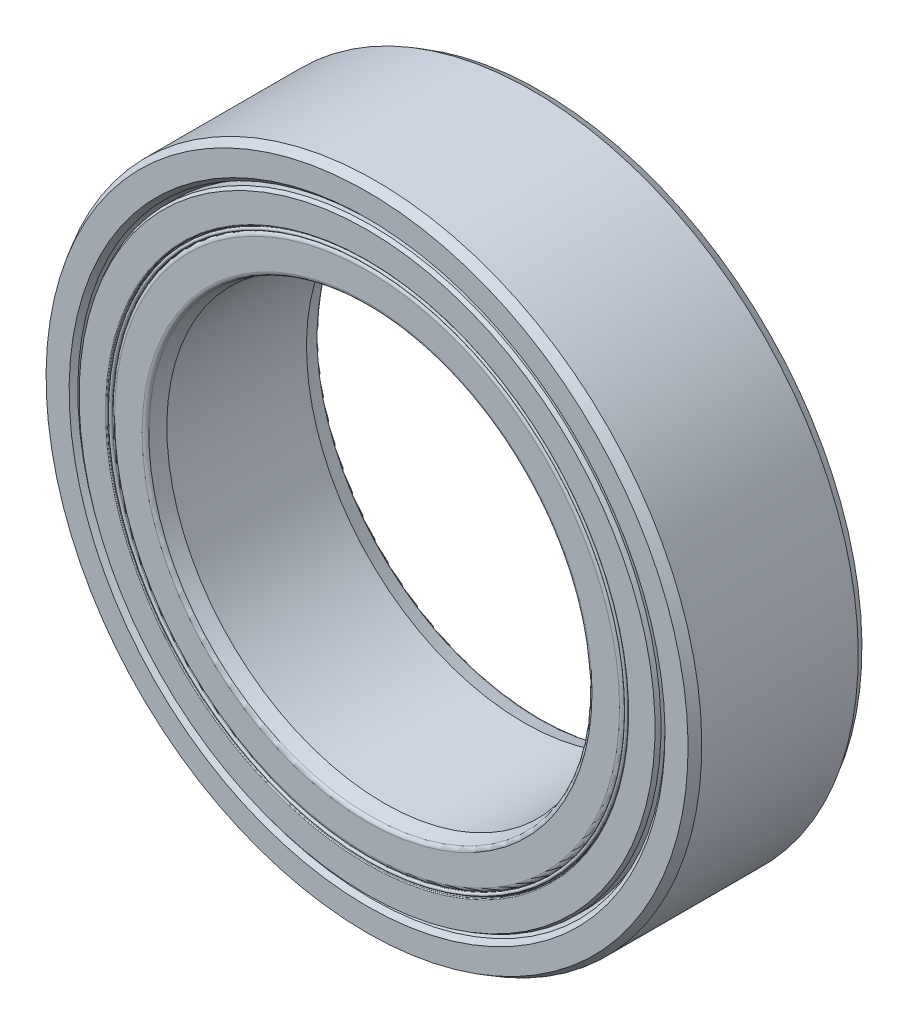
SolidWorks part; units mm, degrees
ref_plane "Front Plane" through (0, 0, 0) normal (0, 0, 1) x (1, 0, 0)
ref_plane "Top Plane" through (0, 0, 0) normal (0, 1, 0) x (1, 0, 0)
ref_plane "Right Plane" through (0, 0, 0) normal (1, 0, 0) x (0, 0, -1)
sketch "Sketch1" plane through (0, 0, 0) normal (0, 0, 1) x (1, 0, 0)
  line L0 (-7.5, 0) -> (7.5, 0) construction
  line L1 (-5, 0) -> (5, 0) construction
  circle A0 centre (0, 0) radius 5 construction
  circle A1 centre (0, 0) radius 7.5 construction
  point P3 (0, 0)
  point P6 (0, 0)
  point P7 (0, -5)
  point P11 (0, -7.5)
  point P12 (0, 5)
  point P13 (0, 7.5)
  dimension "OD" = 15
  dimension "ID" = 10
sketch "Sketch2" plane through (0, 0, 0) normal (1, 0, 0) x (0, 0, -1)
  line L0 (-2, 7.5) -> (2, 7.5) construction
  line L1 (0, 7.5) -> (0, -7.5) construction
  line L2 (1.8, 7.5) -> (-1.8, 7.5)
  line L3 (-1.8, 7.5) -> (-2, 7.3845)
  line L4 (-2, 7.3845) -> (-2, 6.854)
  line L5 (-1.683, 6.675) -> (-0.8537, 6.675)
  line L6 (1.683, 6.675) -> (0.8537, 6.675)
  line L7 (2, 7.3845) -> (2, 6.854)
  line L8 (1.8, 7.5) -> (2, 7.3845)
  line L9 (-0.8537, 6.675) -> (-0.8537, 6.95) construction
  line L10 (-0.8537, 6.95) -> (-0.8537, 7.225) construction
  line L11 (0, 7.5) -> (0, -7.5) construction
  line L12 (-2, 0) -> (2, 0) construction
  line L13 (2, 5) -> (-2, 5) construction
  line L14 (-2, 5) -> (-2, -5) construction
  line L15 (-2, -5) -> (2, -5) construction
  line L16 (2, 7.5) -> (2, -7.5) construction
  line L17 (-0.8537, 7.225) -> (-0.8537, 7.5) construction
  line L18 (-0.8537, 7.225) -> (0, 7.225) construction
  line L20 (-1.683, 6.675) -> (-1.9, 6.754)
  line L21 (-1.9, 6.754) -> (-2, 6.854)
  line L26 (1.9, 6.754) -> (2, 6.854)
  line L27 (1.683, 6.675) -> (1.9, 6.754)
  arc A0 (-0.8537, 6.675) -> (0.8537, 6.675) centre (0, 6.2875) cw
  circle A1 centre (0, 6.2875) radius 0.9375 construction
  point P17 (0, 0)
  point P21 (0, 7.5)
  point P30 (0, -5)
  dimension "Approx. Ball Dia." = 1.875
  dimension "Width" = 4
  dimension "For Shaft Diameter" = 10
  dimension "For Housing ID" = 15
  dimension "D4" = 13.35
  dimension "D2" = 20
  dimension "D5" = 45
  dimension "D1" = 30
  dimension "D6" = 0.2
  dimension "D7" = 0.1
sketch "Sketch3" plane through (0, 0, 0) normal (1, 0, 0) x (0, 0, -1)
  line L14 (-1.683, 6.675) -> (-1.9, 6.754) construction
  line L15 (-1.9, 6.754) -> (-2, 6.854) construction
  line L16 (-2, 7.3845) -> (-2, 6.854) construction
  line L17 (-1.8, 7.5) -> (-2, 7.3845) construction
  line L18 (1.8, 7.5) -> (-1.8, 7.5) construction
  line L19 (1.8, 7.5) -> (2, 7.3845) construction
  line L20 (2, 7.3845) -> (2, 6.854) construction
  line L21 (1.9, 6.754) -> (2, 6.854) construction
  line L22 (1.683, 6.675) -> (1.9, 6.754) construction
  line L23 (1.683, 6.675) -> (0.8537, 6.675) construction
  line L24 (-1.683, 6.675) -> (-0.8537, 6.675) construction
  line L25 (-1.683, 6.675) -> (-1.9, 6.754)
  line L26 (-1.9, 6.754) -> (-2, 6.854)
  line L27 (-2, 7.3845) -> (-2, 6.854)
  line L28 (-1.8, 7.5) -> (-2, 7.3845)
  line L29 (1.8, 7.5) -> (-1.8, 7.5)
  line L30 (1.8, 7.5) -> (2, 7.3845)
  line L31 (2, 7.3845) -> (2, 6.854)
  line L32 (1.9, 6.754) -> (2, 6.854)
  line L33 (1.683, 6.675) -> (1.9, 6.754)
  line L34 (1.683, 6.675) -> (0.8537, 6.675)
  line L35 (-1.683, 6.675) -> (-0.8537, 6.675)
  arc A2 (0.8537, 6.675) -> (-0.8537, 6.675) centre (0, 6.2875) ccw construction
  arc A3 (0.8537, 6.675) -> (-0.8537, 6.675) centre (0, 6.2875) ccw
revolve "Revolve1" add sketch "Sketch3" angle 360 about L12
sketch "Sketch4" plane through (0, 0, 0) normal (1, 0, 0) x (0, 0, -1)
  line L0 (0, 7.5) -> (0, -7.5) construction
  line L1 (0, 7.5) -> (0, -7.5) construction
  line L2 (-1.6063, 5) -> (-1.9329, 5.0875)
  line L3 (-2, 5.175) -> (-2, 5.8094)
  line L4 (2, -7.3845) -> (2, 7.3845) construction
  line L5 (-1.9094, 5.9) -> (-0.8537, 5.9)
  line L6 (-1.6063, 5) -> (1.6063, 5)
  line L7 (2, 7.3845) -> (2, 6.854) construction
  line L8 (1.6063, 5) -> (1.9329, 5.0875)
  line L9 (0, 7.225) -> (0, 5) construction
  line L10 (2, 5.175) -> (2, 5.8094)
  line L11 (1.9094, 5.9) -> (0.8537, 5.9)
  line L12 (1.6063, 5) -> (1.6063, 5.0875) construction
  line L13 (1.6063, 5.0875) -> (1.6063, 5.175) construction
  line L14 (1.6063, 5.175) -> (1.6063, 5.2625) construction
  line L15 (1.6063, 5.2625) -> (1.6063, 5.35) construction
  circle A0 centre (0, 6.2875) radius 0.9375 construction
  arc A1 (0.8537, 5.9) -> (-0.8537, 5.9) centre (0, 6.2875) cw
  arc A2 (2, 5.8094) -> (1.9094, 5.9) centre (1.9094, 5.8094) ccw
  arc A3 (-2, 5.8094) -> (-1.9094, 5.9) centre (-1.9094, 5.8094) cw
  arc A4 (1.9329, 5.0875) -> (2, 5.175) centre (1.9094, 5.175) ccw
  arc A5 (-1.9329, 5.0875) -> (-2, 5.175) centre (-1.9094, 5.175) cw
  point P14 (2, 5.1055)
  point P36 (0, 5.35)
  dimension "D1" = 15
revolve "Revolve2" add sketch "Sketch4" angle 360 about L12
sketch "Sketch5" plane through (0, 0, 0) normal (1, 0, 0) x (0, 0, -1)
  line L0 (-0.9375, 6.2875) -> (0.9375, 6.2875)
  arc A2 (-0.9375, 6.2875) -> (0.9375, 6.2875) centre (0, 6.2875) cw
  arc A3 (0.8537, 6.675) -> (-0.8537, 6.675) centre (0, 6.2875) ccw construction
revolve "Revolve3" add sketch "Sketch5" angle 360 about L0
pattern_circular "CirPattern1" count 14 over 360 about axis through (0, 0, 2) along (0, 0, -1) of bodies 104
sketch "Sketch6" plane through (0, 0, 0) normal (1, 0, 0) x (0, 0, -1)
  line L1 (-1.9134, 6.675) -> (-0.9375, 6.675)
  line L2 (-2, 6.625) -> (-2, 6.02)
  line L3 (-1.98, 6) -> (-0.9375, 6)
  line L4 (-0.9375, 6.675) -> (-0.9375, 6)
  line L5 (-2, 5.175) -> (-2, 5.8094) construction
  line L6 (-1.8, 7.5) -> (-2, 7.3845) construction
  line L7 (0, 7.5) -> (0, 5) construction
  line L8 (1.98, 6) -> (0.9375, 6)
  line L9 (0.9375, 6.675) -> (0.9375, 6)
  line L10 (1.9134, 6.675) -> (0.9375, 6.675)
  line L11 (2, 6.625) -> (2, 6.02)
  line L13 (-1.9094, 5.9) -> (-0.8537, 5.9) construction
  line L14 (-2, 6.625) -> (-1.9134, 6.675)
  line L15 (-1.683, 6.675) -> (-0.8537, 6.675) construction
  line L16 (2, 6.625) -> (1.9134, 6.675)
  arc A0 (-2, 6.02) -> (-1.98, 6) centre (-1.98, 6.02) ccw
  circle A1 centre (0, 6.2875) radius 0.9375 construction
  arc A2 (2, 6.02) -> (1.98, 6) centre (1.98, 6.02) cw
  point P26 (-2, 6)
  dimension "D3" = 0.02
  dimension "D2" = 0.05
revolve "Revolve4" add sketch "Sketch6" angle 360 about L12
sketch "Sketch7" plane through (0, 0, 0) normal (1, 0, 0) x (0, 0, -1)
  line L3 (-0.9375, 6) -> (-1.9147, 6)
  line L4 (-1.98, 6) -> (-0.9375, 6) construction
  line L7 (0, 5.35) -> (0, 5) construction
  line L8 (0, 7.5) -> (0, -7.5) construction
  line L21 (-1.9147, 6) -> (-1.9393, 5.9957)
  line L22 (-1.9375, 5.975) -> (-1.9625, 5.975)
  line L23 (-1.9625, 5.9) -> (-0.9375, 5.9)
  line L24 (-0.9375, 5.9) -> (-0.9375, 6)
  line L25 (-1.9094, 5.9) -> (-0.8537, 5.9) construction
  line L26 (-2, 6.02) -> (-2, 5.9) construction
  line L27 (-2, 5.9) -> (-1.9625, 5.9) construction
  line L28 (-1.9147, 6) -> (-1.9147, 5.975) construction
  line L29 (-1.9147, 5.975) -> (-1.9147, 5.95) construction
  line L30 (-1.9147, 5.95) -> (-1.9147, 5.925) construction
  line L31 (-1.9147, 5.925) -> (-1.9147, 5.9) construction
  circle A2 centre (0, 6.2875) radius 0.9375 construction
  arc A9 (-1.9393, 5.9957) -> (-1.9375, 5.975) centre (-1.9375, 5.9854) ccw
  arc A10 (-1.9625, 5.975) -> (-1.9625, 5.9) centre (-1.9625, 5.9375) ccw
  dimension "D1" = 0.025
  dimension "D2" = 10
revolve "Revolve5" add sketch "Sketch7" angle 360 about L12
equation "\"D4@Sketch2\"=\"OD@Sketch1\"*.89"
equation "\"D1@Sketch6\"=(\"OD@Sketch1\"-\"ID@Sketch1\")*.02"
equation "\"D2@Sketch6\"=\"D1@Sketch6\"*.5"
equation "\"D3@Sketch6\"=\"D1@Sketch6\"*.2"
equation "\"D6@Sketch2\"=\"Width@Sketch2\"*.05"
equation "\"D7@Sketch2\"=\"D6@Sketch2\"*.5"
equation "\"D1@CirPattern1\" =  ( pi * \"OD@Sketch1\" )  * .5625 / \"Approx. Ball Dia.@Sketch2\""
equation "\"Approx. Ball Dia.@Sketch2\"=(\"OD@Sketch1\"-\"ID@Sketch1\")*.5*.75"
